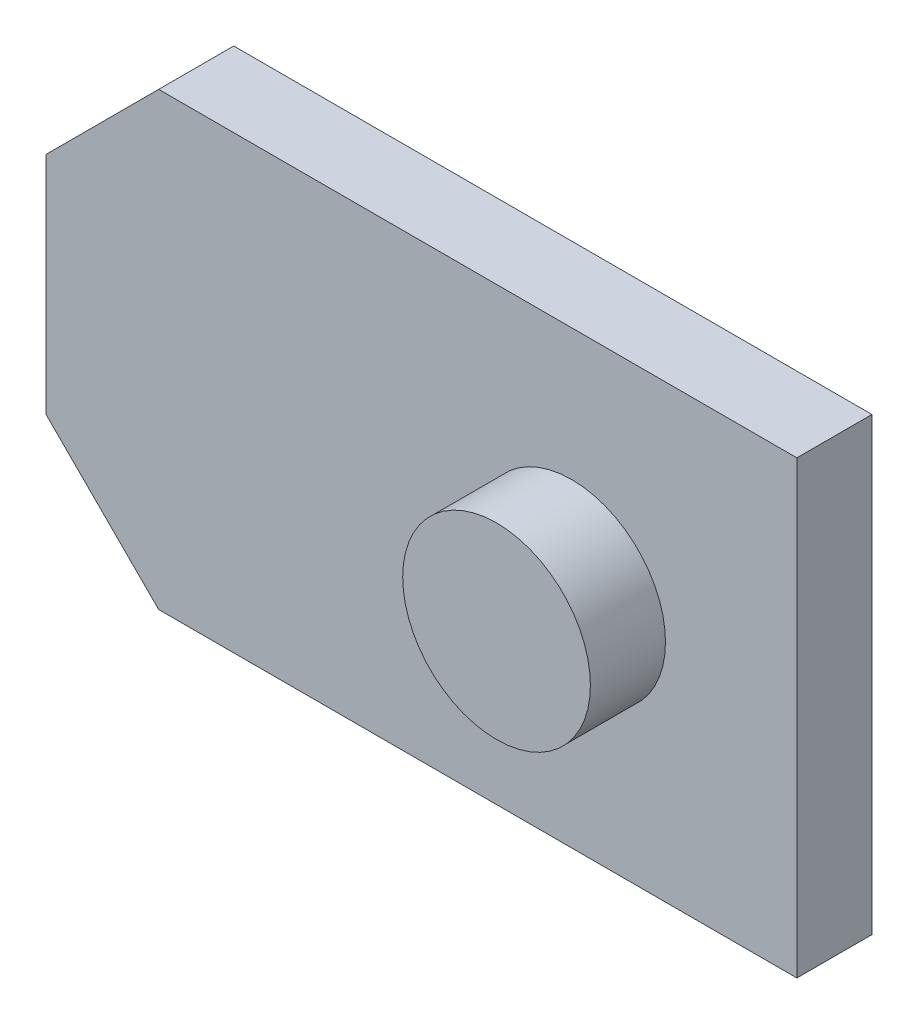
SolidWorks part; units mm, degrees
ref_plane "Front Plane" through (0, 0, 0) normal (0, 0, 1) x (1, 0, 0)
ref_plane "Top Plane" through (0, 0, 0) normal (0, 1, 0) x (1, 0, 0)
ref_plane "Right Plane" through (0, 0, 0) normal (1, 0, 0) x (0, 0, -1)
ref_axis "X" through (-88.99, 0, 0) along (1, 0, 0)
ref_axis "Y" through (0, 55, 0) along (0, -1, 0)
ref_axis "Z" through (0, 0, -88.99) along (0, 0, 1)
sketch "Base Sketch" plane through (0, 0, 0) normal (0, 0, 1) x (1, 0, 0)
  line L0 (-30, 30) -> (-55, 30)
  line L1 (-30, 30) -> (30, 30)
  line L2 (-30, 30) -> (-30, -30)
  line L3 (-30, -30) -> (30, -30)
  line L4 (30, 30) -> (30, -30)
  line L5 (-30, 30) -> (30, -30) construction
  line L6 (-30, -30) -> (30, 30) construction
  line L7 (-55, 30) -> (-70, 15)
  line L8 (-70, 15) -> (-70, -15)
  line L9 (-70, -15) -> (-55, -30)
  line L10 (-55, -30) -> (-30, -30)
  circle A0 centre (0, 0) radius 12.5
  dimension "D1" = 45
  dimension "Hole Diameter" = 25
  dimension "Tab Length" = 40
  dimension "Square Width" = 60
  dimension "Tab End Length" = 30
extrude "Boss-Extrude1" add sketch "Base Sketch" along normal blind 10 contours L9 L10 L2 L0 L7 L8 | L4 L1 L2 L3 A0 region at (-48.4483, 0, 0) region at (0, 29.1515, 0)
extrude "Boss-Extrude2" add sketch "Base Sketch<3>" along normal blind 20 contours A0 region at (0, 0, 0)
sketch "Base Sketch<3>" plane through (0, 0, 0) normal (0, 0, 1) x (1, 0, 0) same geometry as "Base Sketch"
equation "\"Tck\"=10"
equation "\"D1@Boss-Extrude1\"=\"Tck\""
equation "\"D1@Boss-Extrude2\"=\"Tck\"*2"
